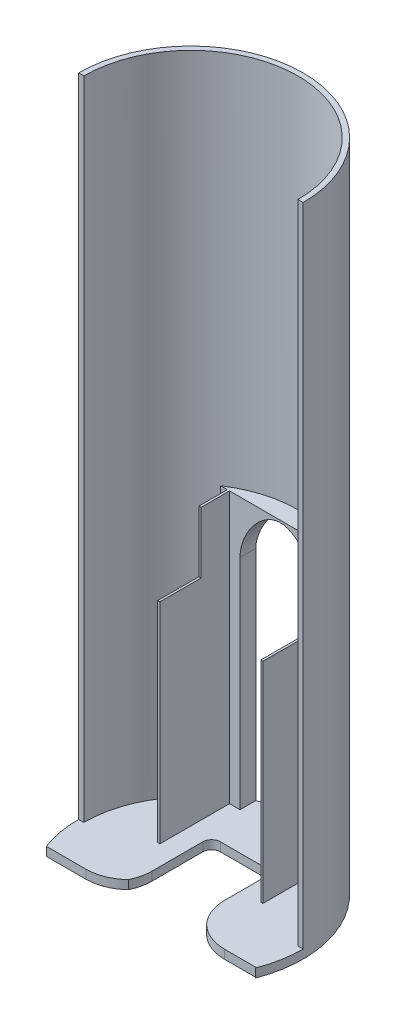
SolidWorks part; units mm, degrees
ref_plane "Front Plane" through (0, 0, 0) normal (0, 0, 1) x (1, 0, 0)
ref_plane "Top Plane" through (0, 0, 0) normal (0, 1, 0) x (1, 0, 0)
ref_plane "Right Plane" through (0, 0, 0) normal (1, 0, 0) x (0, 0, -1)
sketch "Sketch1" plane through (0, 0, 0) normal (0, 1, 0) x (1, 0, 0)
  line L0 (-25.7, 0) -> (25.7, 0) construction
  circle A0 centre (0, 0) radius 25.7
  dimension "D1" = 51.4
extrude "Main Cylinder" add sketch "Sketch1" along normal blind 150
sketch "Sketch4" plane through (0, 150, 0) normal (0, 1, 0) x (1, 0, 0)
  line L0 (0, 0) -> (25.7, 0)
  line L1 (25.7, 0) -> (25.7, -40.6)
  line L2 (25.7, -40.6) -> (-25.7, -40.6)
  line L3 (-25.7, -40.6) -> (-25.7, 0)
  line L4 (-25.7, 0) -> (0, 0)
  circle A0 centre (0, 0) radius 24.5
  circle A1 centre (0, 0) radius 25.7 construction
  circle M1 centre (0, 0) radius 25.7
  dimension "D1" = 1.2
extrude "Main cut down" cut sketch "Sketch4" against normal blind 148 contours L4 A0 L0 | A0 L4 L0 M1 | L0 A0 L4
sketch "Sketch7" plane through (0, 2, 0) normal (0, 1, 0) x (1, 0, 0)
  line L0 (0, -20) -> (0, -10.5488) construction
  line L1 (0, 4.9512) -> (0, 22.8689) construction
  line L2 (-12.05, 20.4512) -> (12.05, 20.4512)
  line L3 (-12.05, 20.4512) -> (-12.05, -10.5488)
  line L4 (-12.05, -10.5488) -> (12.05, -10.5488)
  line L5 (12.05, 20.4512) -> (12.05, -10.5488)
  line L6 (-12.05, 20.4512) -> (12.05, -10.5488) construction
  line L7 (-12.05, -10.5488) -> (12.05, 20.4512) construction
  circle A2 centre (0, 0) radius 25.7 construction
  point P8 (0, 4.9512)
  dimension "D1" = 31
  dimension "D2" = 24.1
extrude "Feather box" add sketch "Sketch7" along normal blind 62
sketch "Sketch8" plane through (0, 64, 0) normal (0, 1, 0) x (1, 0, 0)
  line L0 (0, 20.4512) -> (0, -10.5488) construction
  line L1 (12.05, 20.4512) -> (-12.05, 20.4512) construction
  line L2 (-12.05, -10.5488) -> (12.05, -10.5488) construction
  line L3 (-12.05, 20.4512) -> (12.05, 20.4512) construction
  line L4 (-11.55, 20.4512) -> (11.55, 20.4512)
  line L5 (-11.55, 20.4512) -> (-11.55, -11.5488)
  line L6 (-11.55, -11.5488) -> (11.55, -11.5488)
  line L7 (11.55, 20.4512) -> (11.55, -11.5488)
  line L8 (-11.55, 20.4512) -> (11.55, -11.5488) construction
  line L9 (-11.55, -11.5488) -> (11.55, 20.4512) construction
  point P6 (0, 4.4512)
  dimension "D1" = 0
  dimension "D2" = 23.1
  dimension "D3" = 32
extrude "Feather hole" cut sketch "Sketch8" against normal blind 62 and the other way blind 90
sketch "Sketch15" plane through (0, 2, 0) normal (0, 1, 0) x (1, 0, 0)
  line L1 (-13.5756, 20.3949) -> (13.5756, 20.3949)
  arc A0 (24.5, 0) -> (-24.5, 0) centre (0, 0) ccw construction
  arc A1 (-13.5756, 20.3949) -> (13.5756, 20.3949) centre (0, 0) cw
extrude "window filler" add sketch "Sketch15" along normal blind 62
sketch "Sketch18" plane through (0, 0, -20.3949) normal (0, 0, 1) x (1, 0, 0)
  line L1 (-9.15, 52) -> (9.15, 52)
  line L2 (-9.15, 52) -> (-9.15, 2)
  line L3 (-9.15, 2) -> (9.15, 2)
  line L4 (9.15, 52) -> (9.15, 2)
  line L7 (-13.5756, 2) -> (-12.05, 2) construction
  line L8 (-9.15, 52) -> (9.15, 52)
  line L9 (0, 64) -> (0, 63.5) construction
  spline S0 degree 3 poles (-8.678, 46.988) (-9.6552, 56.332) (-0.1622, 69.2765) (8.5591, 57.2029) (9.893, 47.0898) (-8.678, 46.988) (-9.6552, 56.332) (-0.1622, 69.2765) knots -0.373098 -0.306092 -0.03401 0 0.329949 0.626902 0.693908 0.96599 1 1.329949 1.626902 1.693908 only from (-9.15, 52) to (-9.15, 52)
  dimension "D4" = 50
extrude "window cut" cut sketch "Sketch18" against normal blind 16 contours S0 L4 L1 | S0 L1 | L4 S0 L2 L3
sketch "Sketch23" plane through (0, 2, 0) normal (0, 1, 0) x (1, 0, 0)
  line L0 (0, -6.21) -> (-7.05, -6.21) construction
  line L1 (-8.05, -11.21) -> (9.8, -11.21)
  line L2 (-8.05, -11.21) -> (-8.05, -6.21)
  line L4 (9.8, -11.21) -> (9.8, -6.21)
  line L5 (-8.05, -6.21) -> (-7.05, -6.21)
  line L6 (-7.05, -6.21) -> (7.05, -6.21) construction
  line L7 (-7.05, -6.21) -> (-7.05, 11.79) construction
  line L8 (-7.05, 11.79) -> (7.05, 11.79) construction
  line L9 (7.05, -6.21) -> (7.05, 11.79) construction
  line L10 (9.8, -6.21) -> (7.05, -6.21)
  line L11 (-7.05, -6.21) -> (-7.05, 11.79)
  line L12 (-7.05, 11.79) -> (7.05, 11.79)
  line L13 (7.05, 11.79) -> (7.05, -6.21)
  dimension "D1" = 2.75
  dimension "D2" = 5
  dimension "D3" = 1
  dimension "D5" = 18
extrude "sd reset access" cut sketch "Sketch23" against normal blind 2
sketch "Sketch26" plane through (0, 0, 10.5488) normal (0, 0, 1) x (1, 0, 0)
  line L0 (-11.55, 2) -> (-11.55, 64) construction
  line L1 (-12.05, 2) -> (-11.55, 2)
  line L2 (-12.05, 2) -> (-12.05, 64)
  line L3 (-12.05, 64) -> (-11.55, 64)
  line L4 (-11.55, 2) -> (-11.55, 64)
  line L5 (12.05, 64) -> (12.05, 2) construction
  line L6 (11.55, 2) -> (12.05, 2)
  line L7 (11.55, 2) -> (11.55, 64)
  line L8 (11.55, 64) -> (12.05, 64)
  line L9 (12.05, 2) -> (12.05, 64)
  dimension "D2" = 0
  dimension "D4" = 0
extrude "trim" cut sketch "Sketch26" against normal blind 15
fillet "Fillet3" radius 10 1 edges at (-7.05, 1, 6.21)
sketch "Sketch28" plane through (0, 0, -20.3949) normal (0, 0, 1) x (1, 0, 0)
  line L8 (11.55, 4) -> (9.15, 4)
  line L9 (11.55, 4) -> (11.55, 12)
  line L10 (11.55, 12) -> (9.15, 12)
  line L11 (9.15, 4) -> (9.15, 12)
  dimension "D6" = 8
sketch "Sketch34" plane through (0, 2, 0) normal (0, 1, 0) x (1, 0, 0)
  line L1 (-25.1065, -26.4838) -> (24.0082, -26.4838)
  line L2 (-25.1065, -26.4838) -> (-25.1065, -9.0263)
  line L3 (-25.1065, -9.0263) -> (24.0082, -9.0263)
  line L4 (24.0082, -26.4838) -> (24.0082, -9.0263)
extrude "Cut-Extrude5" cut sketch "Sketch34" against normal blind 2 contours L2 L3 L4 L1
fillet "Fillet7" radius 10 1 edges at (-8.05, 1, 9.0263)
fillet "Fillet8" radius 10 2 edges at (9.8, 1, 9.0263) (7.05, 1, 6.21)
fillet "Fillet9" radius 2 2 edges at (-7.05, 1, -11.79) (7.05, 1, -11.79)
extrude "Cut-Extrude6" cut sketch "Sketch28" against normal blind 10
fillet "Fillet10" radius 10 1 edges at (9.15, 12, -22.2055)
fillet "Fillet11" radius 2 1 edges at (9.15, 4, -22.2055)
sketch "Sketch35" plane through (0, 64, 0) normal (0, 1, 0) x (1, 0, 0)
  line L0 (-11.55, 4.4512) -> (-11.55, 20.3949) construction
  line L1 (-12.05, 4.4512) -> (-11.55, 4.4512)
  line L2 (-12.05, 4.4512) -> (-12.05, 13.8958)
  line L3 (-12.05, 13.8958) -> (-11.55, 13.8958)
  line L4 (-11.55, 4.4512) -> (-11.55, 13.8958)
  line L5 (11.55, 4.4512) -> (11.55, 20.3949) construction
  line L6 (12.05, 4.4512) -> (11.55, 4.4512)
  line L7 (12.05, 4.4512) -> (12.05, 13.8958)
  line L8 (12.05, 13.8958) -> (11.55, 13.8958)
  line L9 (11.55, 4.4512) -> (11.55, 13.8958)
extrude "Cut-Extrude7" cut sketch "Sketch35" against normal blind 14
